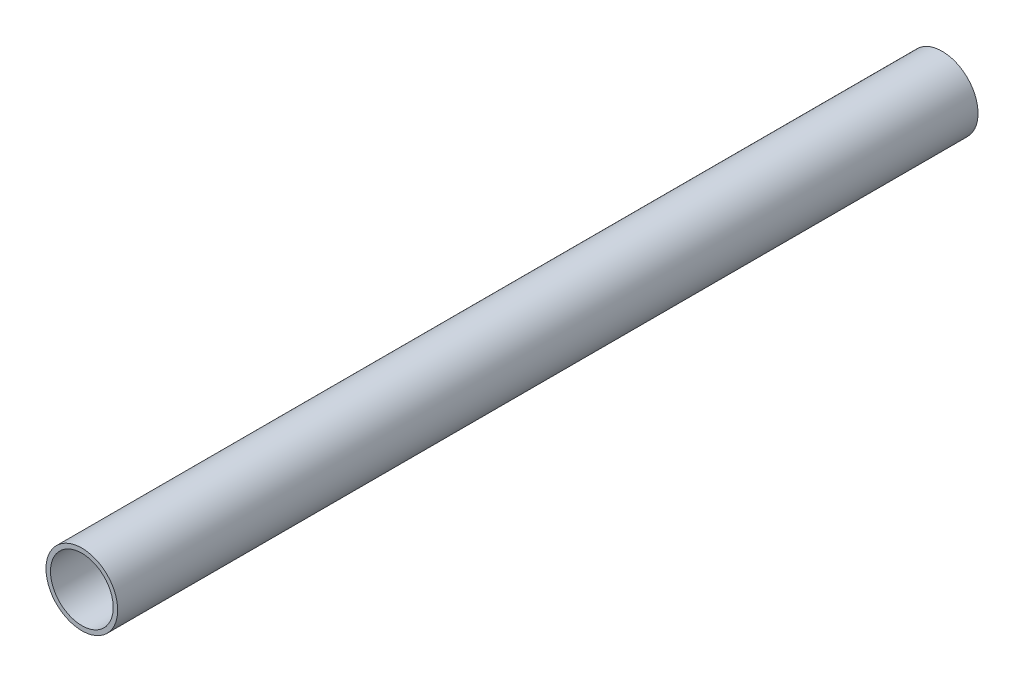
SolidWorks part; units mm, degrees
material "PC High Viscosity"
ref_plane "Front Plane" through (0, 0, 0) normal (0, 0, 1) x (1, 0, 0)
ref_plane "Top Plane" through (0, 0, 0) normal (0, 1, 0) x (1, 0, 0)
ref_plane "Right Plane" through (0, 0, 0) normal (1, 0, 0) x (0, 0, -1)
sketch "Sketch1" plane through (0, 0, 0) normal (0, 0, 1) x (1, 0, 0)
  circle A0 centre (0, 0) radius 22.225
  circle A1 centre (0, 0) radius 25.4
  dimension "D1" = 50.8
  dimension "D2" = 44.45
extrude "Boss-Extrude1" add sketch "Sketch1" along normal mid plane 609.6
